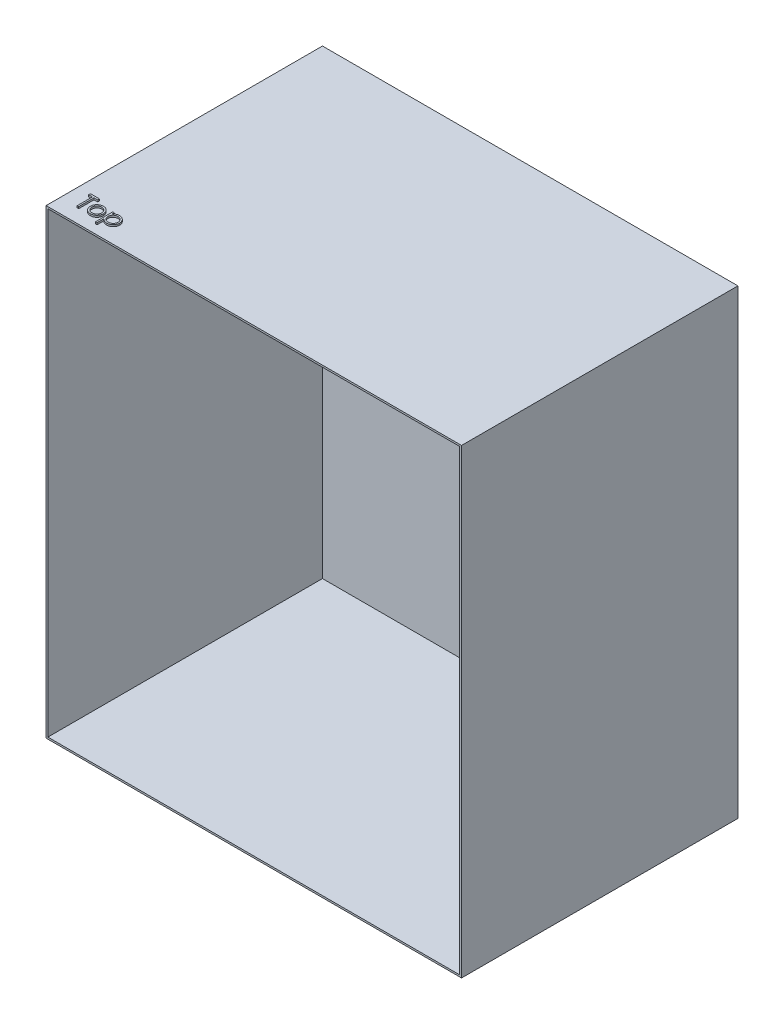
SolidWorks part; units mm, degrees
ref_plane "Front Plane" through (0, 0, 0) normal (0, 0, 1) x (1, 0, 0)
ref_plane "Top Plane" through (0, 0, 0) normal (0, 1, 0) x (1, 0, 0)
ref_plane "Right Plane" through (0, 0, 0) normal (1, 0, 0) x (0, 0, -1)
sketch "Sketch1" plane through (0, 0, 0) normal (0, 0, 1) x (1, 0, 0)
  line L0 (-230.6, 256) -> (230.6, 256)
  line L1 (-228.6, 254) -> (228.6, 254)
  line L2 (-228.6, 254) -> (-228.6, -254)
  line L3 (-228.6, -254) -> (228.6, -254)
  line L4 (228.6, 254) -> (228.6, -254)
  line L5 (230.6, 256) -> (230.6, -256)
  line L6 (-230.6, -256) -> (230.6, -256)
  line L7 (-230.6, 256) -> (-230.6, -256)
  dimension "D1" = 457.2
  dimension "D2" = 508
  dimension "D3" = 228.6
  dimension "D4" = 254
  dimension "D5" = 2
extrude "Boss-Extrude1" add sketch "Sketch1" against normal blind 2 contours L0 L5 L6 L7
extrude "Boss-Extrude4" add sketch "Sketch1<6>" along normal blind 304.8
sketch "Sketch1<6>" plane through (0, 0, 0) normal (0, 0, 1) x (1, 0, 0) same geometry as "Sketch1"
sketch "Sketch4" plane through (0, 256, 0) normal (0, 1, 0) x (1, 0, 0)
  line L0 (-230.6, 2) -> (-230.6, -304.8) construction
  line L1 (230.6, -304.8) -> (-230.6, -304.8) construction
  text T0 "Top" font "Century Gothic" height in points 72
  dimension "D1" = 15
  dimension "D2" = 15
extrude "Boss-Extrude5" add sketch "Sketch4" along normal blind 2
equation "\"D4@Sketch1\"=\"D2@Sketch1\"/2"
equation "\"D3@Sketch1\"=\"D1@Sketch1\"/2"
